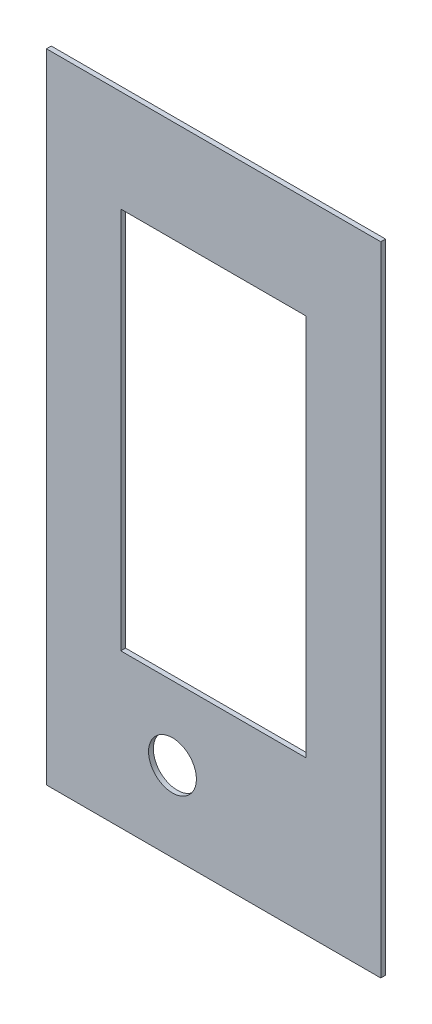
SolidWorks part; units mm, degrees
ref_plane "Спереди" through (0, 0, 0) normal (0, 0, 1) x (1, 0, 0)
ref_plane "Сверху" through (0, 0, 0) normal (0, 1, 0) x (1, 0, 0)
ref_plane "Справа" through (0, 0, 0) normal (1, 0, 0) x (0, 0, -1)
sketch "Эскиз1" plane through (0, 0, 0) normal (0, 1, 0) x (1, 0, 0)
  line L1 (-144.7882, -2.3414) -> (134.7883, -2.3414)
  line L2 (-144.7882, -2.3414) -> (-144.7882, -6.3414)
  line L3 (-144.7882, -6.3414) -> (134.7883, -6.3414)
  line L4 (134.7883, -2.3414) -> (134.7883, -6.3414)
extrude "Вытянуть1" add sketch "Эскиз1" along normal up to surface (533.2137 mm away)
sketch "Эскиз2" plane through (0, 0, 2.3414) normal (0, 0, -1) x (-1, 0, 0)
  circle A0 centre (39.3967, 66.9121) radius 20
extrude "Вырез-Вытянуть1" cut sketch "Эскиз2" against normal through all
sketch "Эскиз3" plane through (0, 0, 6.3414) normal (0, 0, 1) x (1, 0, 0)
  line L1 (-82.6488, 448.2137) -> (72.3512, 448.2137)
  line L2 (-82.6488, 448.2137) -> (-82.6488, 128.2137)
  line L3 (-82.6488, 128.2137) -> (72.3512, 128.2137)
  line L4 (72.3512, 448.2137) -> (72.3512, 128.2137)
extrude "Cut-Extrude1" cut sketch "Эскиз3" against normal through all
